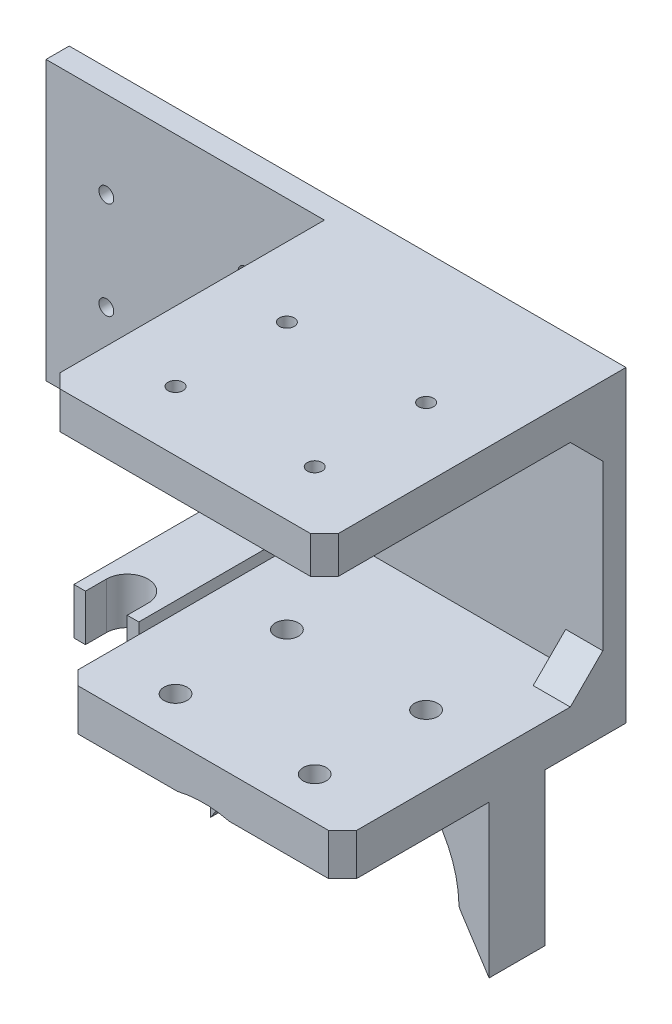
SolidWorks part; units mm, degrees
ref_plane "前视基准面" through (0, 0, 0) normal (0, 0, 1) x (1, 0, 0)
ref_plane "上视基准面" through (0, 0, 0) normal (0, 1, 0) x (1, 0, 0)
ref_plane "右视基准面" through (0, 0, 0) normal (1, 0, 0) x (0, 0, -1)
other "Configuration Table"
sketch "草图1" plane through (0, 0, 0) normal (0, 0, 1) x (1, 0, 0)
  line L0 (-25, 75) -> (-25, 25) construction
  line L2 (35, 20) -> (-85, 20)
  line L3 (35, 20) -> (35, 80)
  line L4 (35, 80) -> (-85, 80)
  line L5 (-85, 20) -> (-85, 80)
  line L6 (35, 20) -> (-85, 80) construction
  line L7 (35, 80) -> (-85, 20) construction
  point P4 (-25, 50)
  dimension "D1" = 60
  dimension "D2" = 120
extrude "凸台-拉伸1" add sketch "草图1" along normal blind 5
sketch "草图2" plane through (0, 0, 0) normal (0, 0, -1) x (-1, 0, 0)
  circle A0 centre (-25, 75) radius 1.75
  circle A1 centre (25, 75) radius 1.75
  circle A2 centre (75, 75) radius 1.75
  circle A3 centre (75, 25) radius 1.75
  circle A4 centre (25, 25) radius 1.75
  circle A5 centre (-25, 25) radius 1.75
  dimension "D1" = 3.5
  dimension "D2" = 3.5
  dimension "D3" = 3.5
  dimension "D4" = 3.5
  dimension "D5" = 3.5
  dimension "D6" = 3.5
sketch "草图3" plane through (0, 0, 5) normal (0, 0, 1) x (1, 0, 0)
  line L0 (-25, 80) -> (-25, 20) construction
  line L1 (35, 80) -> (-85, 80) construction
  line L2 (-85, 20) -> (35, 20) construction
  line L3 (35, 20) -> (35, 80) construction
  line L8 (-25, 80) -> (35, 80)
  line L9 (-25, 80) -> (-25, 72)
  line L10 (-25, 72) -> (35, 72)
  line L11 (35, 80) -> (35, 72)
  point P6 (-25, 50)
  dimension "D1" = 8
extrude "凸台-拉伸3" add sketch "草图3" along normal blind 60
sketch "草图4" plane through (35, 0, 0) normal (1, 0, 0) x (0, 0, -1)
  line L11 (0, -145) -> (0, 145) construction
  line L12 (0, 13.617) -> (-61.0881, 13.617)
  line L13 (0, 13.617) -> (0, 22.617)
  line L14 (0, 22.617) -> (-61.0881, 22.617)
  line L15 (-61.0881, 13.617) -> (-61.0881, 22.617)
  dimension "D1" = 9
extrude "凸台-拉伸4" add sketch "草图4" against normal blind 60
sketch "草图6" plane through (0, 0, 0) normal (0, 0, -1) x (-1, 0, 0)
  line L0 (-5, 13.617) -> (-5, 34.4671) construction
  line L1 (25, 13.617) -> (-35, 13.617) construction
  line L2 (-5, 13.617) -> (-5, -49.7308) construction
  circle A0 centre (-5, -9.2139) radius 23.5
  dimension "D1" = 47
extrude "切除-拉伸1" cut sketch "草图6" against normal through all
sketch "草图7" plane through (0, 0, 0) normal (0, 0, -1) x (-1, 0, 0)
  line L1 (-35, 13.617) -> (25, 13.617)
  line L2 (-35, 13.617) -> (-35, -9.2139)
  line L4 (25, 13.617) -> (25, -9.2139)
  line L5 (-42.9383, -9.2139) -> (32.9383, -9.2139) construction
  line L8 (25, -9.2139) -> (25, -19.2139)
  line L9 (25, -19.2139) -> (18.816, -9.7)
  line L10 (-35, -9.2139) -> (-35, -19.2139)
  line L11 (-35, -19.2139) -> (-28.816, -9.7)
  arc A0 (18.4934, -8.6574) -> (-28.4934, -8.6574) centre (-5, -9.2139) ccw
  arc A1 (18.816, -9.7) -> (18.4934, -8.6574) centre (20.4928, -8.61) cw
  arc A2 (-28.816, -9.7) -> (-28.4934, -8.6574) centre (-30.4928, -8.61) ccw
  point P12 (-5, -9.2139)
  point P17 (18.5, -9.2139)
  point P20 (-28.5, -9.2139)
  line M14 (-35, 13.617) -> (-10.5677, 13.617)
  line M16 (0.5677, 13.617) -> (25, 13.617)
  dimension "D3" = 2
  dimension "D1" = 10
  dimension "D2" = 10
extrude "凸台-拉伸5" add sketch "草图7" against normal blind 50 contours L2 L5 A2 A0 M14 | A1 L5 L4 A0 M16 | L5 A1 L9 L8 | L5 L10 L11 A2 region at (28.467, 4.7822, 0) region at (32.8352, -12.5486, 0) region at (-18.467, 4.7822, 0) region at (-22.8352, -12.5486, 0)
sketch "草图8" plane through (35, 0, 0) normal (1, 0, 0) x (0, 0, -1)
  line L0 (-50, 13.617) -> (-29.5, 13.617)
  line L1 (0, -19.2139) -> (0, 80) construction
  line L2 (-50, -19.2139) -> (0, -19.2139) construction
  line L4 (-29.5, -19.2139) -> (-29.5, 13.617)
  line L5 (-29.5, 13.617) -> (-17.5, 13.617)
  line L6 (-17.5, -19.2139) -> (-17.5, 13.617)
  line L7 (-31, -20.1273) -> (-31, -47.1273) construction
  line L9 (-17.5, -19.2139) -> (0, -19.2139)
  line L10 (0, -19.2139) -> (0, 13.617)
  line L11 (-50, 13.617) -> (-50, -19.2139)
  line L12 (-50, -19.2139) -> (-29.5, -19.2139)
  line L13 (-17.5, 13.617) -> (0, 13.617)
  line M9 (-50, 13.617) -> (-50, -19.2139)
  line M10 (-50, -19.2139) -> (0, -19.2139)
  line M11 (0, -19.2139) -> (0, 80)
  dimension "D1" = 12
  dimension "D2" = 1.5
extrude "切除-拉伸2" cut sketch "草图8" against normal blind 60 contours L4 L0 M10 M9 | L13 L6 M10 M11 region at (35, -2.7984, 39.75) region at (35, -2.7984, 8.75)
sketch "草图9" plane through (0, 20, 0) normal (0, -1, 0) x (1, 0, 0)
  line L0 (-85, 0) -> (-25, 0) construction
  line L3 (-32.5, 0) -> (-41.5, 0)
  line L6 (-41.5, 0) -> (-44, 0)
  line L7 (-41.5, 35.5) -> (-41.5, 40)
  line L8 (-41.5, 40) -> (-44, 40)
  line L9 (-44, 0) -> (-44, 40)
  line L10 (-32.5, 0) -> (-30, 0)
  line L11 (-32.5, 35.5) -> (-32.5, 40)
  line L12 (-32.5, 40) -> (-30, 40)
  line L13 (-30, 0) -> (-30, 40)
  arc A0 (-41.5, 35.5) -> (-32.5, 35.5) centre (-37, 35.5) ccw
  dimension "D1" = 9
  dimension "D2" = 2.5
  dimension "D3" = 40
  dimension "D4" = 2.5
  dimension "D5" = 40
extrude "凸台-拉伸6" add sketch "草图9" along normal blind 10
sketch "草图11" plane through (0, 72, 0) normal (0, -1, 0) x (-1, 0, 0)
  circle A0 centre (-20, -52.0881) radius 1.6
  circle A1 centre (10, -28.0881) radius 1.6
  circle A2 centre (-20, -28.0881) radius 1.6
  circle A3 centre (10, -52.0881) radius 1.6
  point P3 (10, -52.0881)
  point P4 (10, -28.0881)
  point P5 (-20, -28.0881)
extrude "切除-拉伸3" cut sketch "草图11" against normal through all
sketch "草图12" plane through (0, 0, 0) normal (0, 0, -1) x (-1, 0, 0)
  line L0 (42, 67.85) -> (42, 62.85) construction
  line L1 (42, 33.65) -> (42, 38.65) construction
  line L2 (72, 33.65) -> (72, 38.65) construction
  circle A0 centre (42, 40.25) radius 1.6
  circle A1 centre (42, 61.25) radius 1.6
  arc A2 (44.1, 65.75) -> (39.9, 65.75) centre (42, 65.75) ccw construction
  arc A3 (39.9, 35.75) -> (44.1, 35.75) centre (42, 35.75) ccw construction
  circle A4 centre (72, 40.25) radius 1.6
  circle A5 centre (72, 61.25) radius 1.6
  arc A7 (69.9, 35.75) -> (74.1, 35.75) centre (72, 35.75) ccw construction
  dimension "D1" = 3.2
  dimension "D2" = 3.2
  dimension "D3" = 5
  dimension "D5" = 3.2
  dimension "D6" = 3.2
  dimension "D7" = 5
  dimension "D4" = 5
extrude "切除-拉伸4" cut sketch "草图12" against normal through all
sketch "草图13" plane through (35, 0, 0) normal (1, 0, 0) x (0, 0, -1)
  line L0 (-5, 65) -> (-12, 72)
  line L1 (-5, 22.617) -> (-5, 72) construction
  line L2 (-65, 72) -> (-5, 72) construction
  dimension "D1" = 7
  dimension "D2" = 7
rib "筋1" sketch "草图13" sketch "草图13" thickness 8 extrusion direction parallel to sketch draft on no parameters "D1"=8
ref_plane "基准面1" through (5, 0, 0) normal (1, 0, 0) x (0, 0, -1)
mirror "镜向1" about plane through (5, 0, 0) normal (1, 0, 0) of "筋1"
ref_plane "基准面2" through (0, 47.3085, 0) normal (0, -1, 0) x (-1, 0, 0)
mirror "镜向2" about plane through (0, 47.3085, 0) normal (0, -1, 0) of "镜向1", "筋1"
sketch "草图15" plane through (0, 0, 0) normal (0, 0, -1) x (-1, 0, 0)
  line L0 (44, 10) -> (44, 20) construction
  line L1 (25, 13.617) -> (30, 13.617)
  line L2 (25, 13.617) -> (25, 20)
  line L3 (25, 20) -> (30, 20)
  line L4 (30, 13.617) -> (30, 20)
  line L5 (44, 13.617) -> (49, 13.617)
  line L6 (44, 13.617) -> (44, 20)
  line L7 (44, 20) -> (49, 20)
  line L8 (49, 13.617) -> (49, 20)
  line L9 (85, 20) -> (44, 20) construction
  dimension "D1" = 5
extrude "凸台-拉伸7" add sketch "草图15" against normal blind 10
chamfer "倒角2" distance 2 angle 45 1 edges at (-49, 16.8085, 10)
chamfer "倒角3" distance 3 angle 45 4 edges at (-25, 18.117, 61.0881) (-25, 76, 65) (35, 18.117, 61.0881) (35, 76, 65)
sketch "草图16" plane through (0, 22.617, 0) normal (0, 1, 0) x (1, 0, 0)
  circle A0 centre (20, -52.0881) radius 2.5
  circle A1 centre (-10, -52.0881) radius 2.5
  circle A2 centre (-10, -28.0881) radius 2.5
  circle A3 centre (20, -28.0881) radius 2.5
  dimension "D1" = 5
  dimension "D2" = 5
  dimension "D3" = 5
  dimension "D4" = 5
extrude "切除-拉伸5" cut sketch "草图16" against normal through all
sketch "草图18" plane through (0, 0, 0) normal (0, 0, -1) x (-1, 0, 0)
  circle A0 centre (75, 75) radius 3.75
  circle A1 centre (25, 75) radius 3.75
  circle A2 centre (-25, 75) radius 3.75
  circle A3 centre (-25, 25) radius 3.75
  circle A4 centre (25, 25) radius 3.75
  circle A5 centre (75, 25) radius 3.75
  dimension "D1" = 7.5
  dimension "D2" = 7.5
  dimension "D3" = 7.5
  dimension "D4" = 7.5
  dimension "D5" = 7.5
  dimension "D6" = 7.5
extrude "切除-拉伸7" cut sketch "草图18" against normal blind 2
